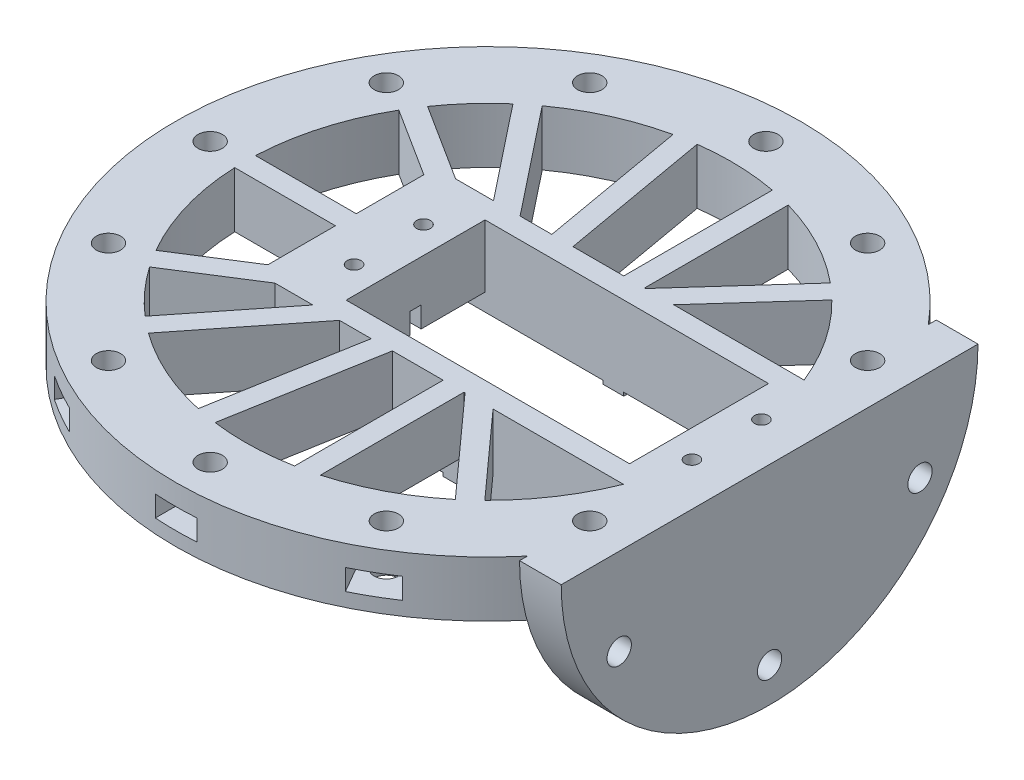
SolidWorks part; units mm, degrees
ref_plane "Front Plane" through (0, 0, 0) normal (0, 0, 1) x (1, 0, 0)
ref_plane "Top Plane" through (0, 0, 0) normal (0, 1, 0) x (1, 0, 0)
ref_plane "Right Plane" through (0, 0, 0) normal (1, 0, 0) x (0, 0, -1)
sketch "Sketch1" plane through (0, 0, 0) normal (0, 1, 0) x (1, 0, 0)
  line L0 (-43.0464, 0) -> (41.9462, 0) construction
  line L1 (0, 43.1152) -> (0, -41.8775) construction
  circle A1 centre (0, 0) radius 45
  dimension "D2" = 90
extrude "Boss-Extrude1" add sketch "Sketch1" along normal blind 12
sketch "Sketch2" plane through (0, 0, 0) normal (0, -1, 0) x (1, 0, 0)
  circle A0 centre (0, 0) radius 35
  dimension "D1" = 70
extrude "Cut-Extrude1" cut sketch "Sketch2" against normal blind 0.5
sketch "Sketch3" plane through (0, 0.5, 0) normal (0, -1, 0) x (1, 0, 0)
  line L0 (35, 0) -> (-35, 0) construction
  line L1 (0, -35) -> (0, 35) construction
  line L3 (37.5324, -10) -> (-17.4676, -10)
  line L4 (37.5324, -10) -> (37.5324, 10)
  line L5 (37.5324, 10) -> (-17.4676, 10)
  line L6 (-17.4676, -10) -> (-17.4676, 10)
  circle A0 centre (0, 0) radius 35 construction
  circle A1 centre (0, 0) radius 35 construction
  dimension "D1" = 20
  dimension "D2" = 55
  dimension "D3" = 10
  dimension "D4" = 37.5324
extrude "Cut-Extrude2" cut sketch "Sketch3" against normal blind 2.5 and the other way up to next
sketch "Sketch4" plane through (0, 3, 0) normal (0, -1, 0) x (1, 0, 0)
  line L0 (37.5324, 0) -> (-17.4676, 0) construction
  line L1 (37.5324, 10) -> (37.5324, -10) construction
  line L2 (-17.4676, 10) -> (-17.4676, -10) construction
  line L3 (0, -10) -> (0, 10) construction
  line L4 (-17.4676, -10) -> (33.541, -10) construction
  line L5 (33.541, 10) -> (-17.4676, 10) construction
  line L7 (30.3722, -10) -> (-10.4278, -10)
  line L8 (30.3722, -10) -> (30.3722, 10)
  line L9 (30.3722, 10) -> (-10.4278, 10)
  line L10 (-10.4278, -10) -> (-10.4278, 10)
  dimension "D1" = 20
  dimension "D2" = 40.8
  dimension "D3" = 30.3722
  dimension "D4" = 10
extrude "Cut-Extrude3" cut sketch "Sketch4" against normal blind 9
sketch "Sketch8" plane through (0, 0.5, 0) normal (0, -1, 0) x (1, 0, 0)
  line L0 (-17.4676, 0) -> (-35, 0) construction
  line L1 (-17.4676, 10) -> (-17.4676, -10) construction
  line L2 (8.0367, 10) -> (8.0367, 34.0648) construction
  line L3 (33.541, 10) -> (-17.4676, 10) construction
  line L4 (8.0367, -10) -> (8.0367, -29.3194) construction
  line L5 (-17.4676, -10) -> (33.541, -10) construction
  line L6 (6.5367, 10) -> (6.5367, 34.3842)
  line L7 (9.5367, 10) -> (9.5367, 33.6757)
  line L8 (9.5367, 10) -> (6.5367, 10)
  line L9 (9.5367, -10) -> (6.5367, -10)
  line L10 (6.5367, -10) -> (6.5367, -34.3842)
  line L11 (9.5367, -10) -> (9.5367, -33.6757)
  line L12 (-17.4676, 1.5) -> (-34.9678, 1.5)
  line L13 (-17.4676, -1.5) -> (-34.9678, -1.5)
  line L14 (-17.4676, 1.5) -> (-17.4676, -1.5)
  arc A0 (33.541, 10) -> (33.541, -10) centre (0, 0) ccw construction
  arc A1 (9.5367, 33.6757) -> (6.5367, 34.3842) centre (7.9531, 33.6757) ccw
  arc A2 (9.5367, -33.6757) -> (6.5367, -34.3842) centre (7.9531, -33.6757) cw
  arc A3 (-34.9678, 1.5) -> (-34.9678, -1.5) centre (-34.9678, 0) ccw
  dimension "D3" = 1.5
  dimension "D1" = 1.5
  dimension "D2" = 1.5
  dimension "D4" = 1.5
extrude "Boss-Extrude2" add sketch "Sketch8" along normal through all
sketch "Sketch16" plane through (0, 3, 0) normal (0, -1, 0) x (1, 0, 0)
  line L0 (-17.4676, 0) -> (37.5324, 0) construction
  line L1 (-17.4676, 10) -> (-17.4676, -10) construction
  line L2 (37.5324, -10) -> (37.5324, 10) construction
  line L3 (30.3722, -0.8) -> (37.5324, -0.8)
  line L4 (-10.4278, -0.8) -> (-17.4676, -0.8)
  line L5 (-10.4278, 10) -> (-10.4278, -10) construction
  line L6 (-10.4278, 0.8) -> (-17.4676, 0.8)
  line L7 (-17.4676, 0.8) -> (-17.4676, -0.8)
  line L8 (-10.4278, 0.8) -> (-10.4278, -0.8)
  line L9 (30.3722, -10) -> (30.3722, 10) construction
  line L10 (30.3722, 0.8) -> (37.5324, 0.8)
  line L11 (37.5324, 0.8) -> (37.5324, -0.8)
  line L12 (30.3722, 0.8) -> (30.3722, -0.8)
  dimension "D1" = 0.8
extrude "Cut-Extrude10" cut sketch "Sketch16" against normal blind 3
sketch "Sketch27" plane through (0, 0, 0) normal (0, -1, 0) x (1, 0, 0)
  line L0 (0, 0) -> (0, -53.17) construction
  line L1 (0, 0) -> (47.7582, -27.5732) construction
  line L3 (31.641, -18.2679) -> (31.641, -21.7321) construction
  line L4 (31.641, -21.7321) -> (34.641, -23.4641) construction
  line L5 (34.641, -23.4641) -> (37.641, -21.7321) construction
  line L6 (37.641, -21.7321) -> (37.641, -18.2679) construction
  line L7 (37.641, -18.2679) -> (34.641, -16.5359) construction
  line L8 (34.641, -16.5359) -> (31.641, -18.2679) construction
  circle A0 centre (0, 0) radius 40 construction
  circle A1 centre (34.641, -20) radius 1.75
  circle A2 centre (0, 0) radius 35 construction
  circle A3 centre (34.641, -20) radius 3 construction
  circle A4 centre (20, -34.641) radius 1.75
  circle A5 centre (0, -40) radius 1.75
  circle A6 centre (-20, -34.641) radius 1.75
  circle A7 centre (-34.641, -20) radius 1.75
  circle A8 centre (-40, 0) radius 1.75
  circle A9 centre (-34.641, 20) radius 1.75
  circle A10 centre (-20, 34.641) radius 1.75
  circle A11 centre (0, 40) radius 1.75
  circle A12 centre (20, 34.641) radius 1.75
  circle A13 centre (34.641, 20) radius 1.75
  circle A15 centre (40, 0) radius 1.75 [skipped]
  point P28 (0, 0)
  point P41 (0, 0)
  dimension "D1" = 80
  dimension "D3" = 3.5
  dimension "D4" = 70
  dimension "D5" = 6
  dimension "D6" = 12
  dimension "D2" = 60
extrude "Cut-Extrude15" cut sketch "Sketch27" against normal through all
ref_plane "Plane1" through (0, 9, 0) normal (0, 1, 0) x (1, 0, 0)
sketch "Sketch28" plane through (0, 9, 0) normal (0, 1, 0) x (1, 0, 0)
  line L0 (0, 0) -> (-54.493, 0) construction
  line L1 (-31.641, 18.2679) -> (-31.641, 21.7321)
  line L2 (-36.5359, 0) -> (-38.2679, 3)
  line L3 (-38.2679, 3) -> (-44.8999, 3)
  line L4 (-31.641, 21.7321) -> (-37.3844, 25.048)
  line L5 (-40.3844, 19.8519) -> (-34.641, 16.5359)
  line L6 (-44.8999, -3) -> (-38.2679, -3)
  line L7 (-38.2679, -3) -> (-36.5359, 0)
  line L8 (-43.4641, 0) -> (-42.5981, -1.5) [skipped]
  line L9 (-41.7321, 3) -> (-42.5981, 1.5) [skipped]
  line L10 (-34.641, 16.5359) -> (-31.641, 18.2679)
  line L11 (-18.2679, 31.641) -> (-16.5359, 34.641)
  line L12 (-16.5359, 34.641) -> (-19.8519, 40.3844)
  line L13 (-25.048, 37.3844) -> (-21.7321, 31.641)
  line L14 (-21.7321, 31.641) -> (-18.2679, 31.641)
  line L15 (0, 36.5359) -> (3, 38.2679)
  line L16 (3, 38.2679) -> (3, 44.8999)
  line L17 (-3, 44.8999) -> (-3, 38.2679)
  line L18 (-3, 38.2679) -> (0, 36.5359)
  line L19 (18.2679, 31.641) -> (21.7321, 31.641)
  line L20 (21.7321, 31.641) -> (25.048, 37.3844)
  line L21 (19.8519, 40.3844) -> (16.5359, 34.641)
  line L22 (16.5359, 34.641) -> (18.2679, 31.641)
  line L23 (31.641, 18.2679) -> (34.641, 16.5359)
  line L24 (34.641, 16.5359) -> (40.3844, 19.8519)
  line L25 (37.3844, 25.048) -> (31.641, 21.7321)
  line L26 (31.641, 21.7321) -> (31.641, 18.2679)
  line L31 (31.641, -18.2679) -> (31.641, -21.7321)
  line L32 (31.641, -21.7321) -> (37.3844, -25.048)
  line L33 (40.3844, -19.8519) -> (34.641, -16.5359)
  line L34 (34.641, -16.5359) -> (31.641, -18.2679)
  line L35 (18.2679, -31.641) -> (16.5359, -34.641)
  line L36 (16.5359, -34.641) -> (19.8519, -40.3844)
  line L37 (25.048, -37.3844) -> (21.7321, -31.641)
  line L38 (21.7321, -31.641) -> (18.2679, -31.641)
  line L39 (0, -36.5359) -> (-3, -38.2679)
  line L40 (-3, -38.2679) -> (-3, -44.8999)
  line L41 (3, -44.8999) -> (3, -38.2679)
  line L42 (3, -38.2679) -> (0, -36.5359)
  line L43 (-18.2679, -31.641) -> (-21.7321, -31.641)
  line L44 (-21.7321, -31.641) -> (-25.048, -37.3844)
  line L45 (-19.8519, -40.3844) -> (-16.5359, -34.641)
  line L46 (-16.5359, -34.641) -> (-18.2679, -31.641)
  line L47 (-31.641, -18.2679) -> (-34.641, -16.5359)
  line L48 (-34.641, -16.5359) -> (-40.3844, -19.8519)
  line L49 (-37.3844, -25.048) -> (-31.641, -21.7321)
  line L50 (-31.641, -21.7321) -> (-31.641, -18.2679)
  line L51 (36.5359, 0) -> (38.2679, -3) [skipped]
  line L52 (38.2679, -3) -> (44.8999, -3) [skipped]
  line L53 (44.8999, 3) -> (38.2679, 3) [skipped]
  line L54 (38.2679, 3) -> (36.5359, 0) [skipped]
  arc A0 (-44.8999, 3) -> (-44.8999, -3) centre (0, 0) ccw
  circle A1 centre (-40, 0) radius 3 construction
  arc A2 (-37.3844, 25.048) -> (-40.3844, 19.8519) centre (0, 0) ccw
  circle A3 centre (-34.641, 20) radius 3 construction
  arc A4 (-19.8519, 40.3844) -> (-25.048, 37.3844) centre (0, 0) ccw
  circle A5 centre (-20, 34.641) radius 3 construction
  arc A6 (3, 44.8999) -> (-3, 44.8999) centre (0, 0) ccw
  circle A7 centre (0, 40) radius 3 construction
  arc A8 (25.048, 37.3844) -> (19.8519, 40.3844) centre (0, 0) ccw
  circle A9 centre (20, 34.641) radius 3 construction
  arc A10 (40.3844, 19.8519) -> (37.3844, 25.048) centre (0, 0) ccw
  circle A11 centre (34.641, 20) radius 3 construction
  arc A14 (37.3844, -25.048) -> (40.3844, -19.8519) centre (0, 0) ccw
  circle A15 centre (34.641, -20) radius 3 construction
  arc A16 (19.8519, -40.3844) -> (25.048, -37.3844) centre (0, 0) ccw
  circle A17 centre (20, -34.641) radius 3 construction
  arc A18 (-3, -44.8999) -> (3, -44.8999) centre (0, 0) ccw
  circle A19 centre (0, -40) radius 3 construction
  arc A20 (-25.048, -37.3844) -> (-19.8519, -40.3844) centre (0, 0) ccw
  circle A21 centre (-20, -34.641) radius 3 construction
  arc A22 (-40.3844, -19.8519) -> (-37.3844, -25.048) centre (0, 0) ccw
  circle A23 centre (-34.641, -20) radius 3 construction
  arc A24 (44.8999, -3) -> (44.8999, 3) centre (0, 0) ccw [skipped]
  circle A25 centre (40, 0) radius 3 construction
  point P94 (0, 0)
  dimension "D1" = 90
  dimension "D2" = 6
  dimension "D3" = 12
extrude "Cut-Extrude17" cut sketch "Sketch28" against normal blind 3
sketch "Sketch29" plane through (0, 0.5, 0) normal (0, -1, 0) x (1, 0, 0)
  line L0 (32.4962, -13) -> (13.7255, -13)
  line L1 (9.5367, -33.6757) -> (9.5367, -10) construction
  line L2 (9.5367, -13) -> (9.5367, -33.6757)
  line L3 (9.5367, -10) -> (33.541, -10) construction
  line L4 (6.5367, -13) -> (-0.7691, -13)
  line L5 (6.5367, -10) -> (6.5367, -34.3842) construction
  line L6 (-20.4676, -11.223) -> (-20.4676, -1.5)
  line L7 (-34.9678, -1.5) -> (-17.4676, -1.5) construction
  line L8 (-20.4676, -1.5) -> (-34.9678, -1.5)
  line L9 (-17.4676, -0.8) -> (-17.4676, -10) construction
  line L10 (32.4962, 13) -> (13.7255, 13)
  line L11 (9.5367, 10) -> (9.5367, 33.6757) construction
  line L12 (9.5367, 13) -> (9.5367, 33.6757)
  line L13 (-7.5493, 34.1761) -> (-3.8154, 13)
  line L14 (6.5367, 13) -> (-0.7691, 13)
  line L15 (6.5367, 34.3842) -> (6.5367, 10) construction
  line L16 (-20.4676, 11.223) -> (-20.4676, 1.5)
  line L17 (-17.4676, 1.5) -> (-34.9678, 1.5) construction
  line L18 (-20.4676, 1.5) -> (-34.9678, 1.5)
  line L19 (6.5367, 13) -> (6.5367, 34.3842)
  line L20 (6.5367, -34.3842) -> (6.5367, -13)
  line L21 (0, 0) -> (-21.7353, -27.4331) construction
  line L22 (-20.5397, -28.3394) -> (-8.3862, -13)
  line L23 (-22.8911, -26.4764) -> (-12.2137, -13)
  line L24 (0, 0) -> (-20.4676, -13) construction
  line L25 (-17.6698, -13) -> (-28.713, -20.0141)
  line L26 (-20.4676, -11.223) -> (-30.3215, -17.4817)
  line L27 (0, 0) -> (-35, 0) construction
  line L28 (-20.4676, 11.223) -> (-30.3215, 17.4817)
  line L29 (-17.6698, 13) -> (-28.713, 20.0141)
  line L30 (-22.8911, 26.4764) -> (-12.2137, 13)
  line L31 (-20.5397, 28.3394) -> (-8.3862, 13)
  line L32 (-12.2137, 13) -> (-17.6698, 13)
  line L33 (0, 0) -> (-6.0777, -34.4683) construction
  line L34 (-4.5949, -34.6971) -> (-0.7691, -13)
  line L35 (-7.5493, -34.1761) -> (-3.8154, -13)
  line L36 (-3.8154, -13) -> (-17.6698, -13)
  line L37 (-4.5949, 34.6971) -> (-0.7691, 13)
  line L38 (-3.8154, 13) -> (-8.3862, 13)
  line L39 (0, 0) -> (23.4214, -26.0084) construction
  line L40 (9.6883, -13) -> (22.2852, -26.9883)
  line L41 (13.7255, -13) -> (24.5145, -24.9808)
  line L42 (13.7255, 13) -> (24.5145, 24.9808)
  line L43 (9.6883, 13) -> (22.2852, 26.9883)
  line L44 (9.6883, -13) -> (9.5367, -13)
  line L45 (9.6883, 13) -> (9.5367, 13)
  arc A0 (9.5367, -33.6757) -> (22.2852, -26.9883) centre (0, 0) ccw
  arc A1 (6.5367, 34.3842) -> (-4.5949, 34.6971) centre (0, 0) ccw
  arc A2 (32.4962, 13) -> (24.5145, 24.9808) centre (0, 0) ccw
  arc A3 (-34.9678, -1.5) -> (-30.3215, -17.4817) centre (0, 0) ccw
  circle A4 centre (0, 0) radius 35 construction
  arc A5 (-7.5493, 34.1761) -> (-20.5397, 28.3394) centre (0, 0) ccw
  arc A6 (-4.5949, -34.6971) -> (6.5367, -34.3842) centre (0, 0) ccw
  arc A7 (-20.5397, -28.3394) -> (-7.5493, -34.1761) centre (0, 0) ccw
  arc A8 (-28.713, -20.0141) -> (-22.8911, -26.4764) centre (0, 0) ccw
  arc A9 (-30.3215, 17.4817) -> (-34.9678, 1.5) centre (0, 0) ccw
  arc A10 (-22.8911, 26.4764) -> (-28.713, 20.0141) centre (0, 0) ccw
  arc A11 (24.5145, -24.9808) -> (32.4962, -13) centre (0, 0) ccw
  arc A12 (22.2852, 26.9883) -> (9.5367, 33.6757) centre (0, 0) ccw
  point P11 (21.5389, -10)
  point P23 (-17.4676, -5.4)
  line M3 (-17.4676, -1.5) -> (-34.9678, -1.5)
  arc M4 (-34.9678, -1.5) -> (6.5367, -34.3842) centre (0, 0) ccw
  line M5 (6.5367, -34.3842) -> (6.5367, -10)
  dimension "D1" = 1.5
  dimension "D2" = 3
  dimension "D3" = 3
  dimension "D4" = 80
  dimension "D5" = 1.5
  dimension "D6" = 1.5
  dimension "D7" = 1.5
sketch "Sketch32" plane through (0, 3, 0) normal (0, -1, 0) x (1, 0, 0)
  line L0 (-17.4676, 0) -> (37.5324, 0) construction
  line L1 (-17.4676, -1.5) -> (-17.4676, 1.5) construction
  line L2 (37.5324, 10) -> (37.5324, -10) construction
  line L3 (10.0324, 0) -> (10.0324, -10) construction
  line L6 (9.5367, -10) -> (33.541, -10) construction
  circle A0 centre (-14.2876, -5) radius 1
  circle A1 centre (-14.2876, 5) radius 1
  circle A2 centre (34.3524, -5) radius 1
  circle A3 centre (34.3524, 5) radius 1
  dimension "D1" = 24.32
  dimension "D3" = 2
  dimension "D2" = 5
extrude "Cut-Extrude21" cut sketch "Sketch32" against normal through all
extrude "Cut-Extrude22" cut sketch "Sketch29" against normal blind 12 contours L28 A9 L18 L16 | L26 L6 M3 M4 | L23 L36 L25 M4 | L35 L36 L22 M4 | L34 L4 M4 M5 | L2 A0 L40 L44 | L41 A11 L0 | L10 A2 L42 | L43 A12 L12 L45 | L19 A1 L37 L14 | L13 A5 L31 L38 | L30 A10 L29 L32 region at (23.89, 0.5, -17.1237) region at (13.9029, 0.5, -24.813) region at (1.8383, 0.5, -24.6789) region at (-27.5459, 0.5, -7.8919) region at (-10.8152, 0.5, -24.1049) region at (-20.9968, 0.5, -18.9781) region at (23.89, 0.5, 17.1237) region at (13.9029, 0.5, 24.813) region at (-10.8152, 0.5, 24.1049) region at (1.8383, 0.5, 24.6789) region at (-27.5459, 0.5, 7.8919) region at (-20.9968, 0.5, 18.9781)
sketch "Sketch33" plane through (0, 0, 0) normal (0, -1, 0) x (1, 0, 0)
  line L0 (37.5324, 0) -> (37.5324, 38.7806) construction
  line L1 (37.5324, 10) -> (37.5324, -10) construction
  line L3 (37.5324, 38.7806) -> (47.0341, 38.7806)
  line L4 (37.5324, 38.7806) -> (37.5324, -37.2389)
  line L5 (37.5324, -37.2389) -> (47.0341, -37.2389)
  line L6 (47.0341, 38.7806) -> (47.0341, -37.2389)
extrude "Cut-Extrude24" cut sketch "Sketch33" against normal through all
sketch "Sketch34" plane through (37.5324, 0, 0) normal (1, 0, 0) x (0, 0, -1)
  line L0 (-24.8258, 12) -> (24.8258, 12) construction
  line L1 (30, 12) -> (-30, 12)
  arc A0 (-30, 12) -> (30, 12) centre (0, 12) ccw
  dimension "D1" = 30
  dimension "D2" = 60
extrude "Boss-Extrude3" add sketch "Sketch34" along normal blind 3
sketch "Sketch35" plane through (37.5324, 0, 0) normal (-1, 0, 0) x (0, 0, 1)
  line L0 (24.8258, 0) -> (10, 0) construction
  line L1 (13, 0) -> (50, 0)
  line L2 (13, 0) -> (13, 4)
  line L3 (13, 4) -> (50, 4)
  line L4 (50, 0) -> (50, 4)
  line L5 (40.3844, 6) -> (37.3844, 6) construction
  line L6 (0, 6) -> (0, 9) construction
  line L7 (-13, 0) -> (-13, 4)
  line L8 (-13, 4) -> (-50, 4)
  line L9 (-13, 0) -> (-50, 0)
  line L10 (-50, 0) -> (-50, 4)
  dimension "D1" = 2
  dimension "D2" = 13
  dimension "D3" = 50
extrude "Cut-Extrude26" cut sketch "Sketch35" along normal blind 90
sketch "Sketch36" plane through (0, 0, 0) normal (0, 0, 1) x (1, 0, 0)
  line L0 (-17.4676, 0) -> (-17.4676, 0.5)
  line L1 (-17.4676, 0.5) -> (-20.4676, 0.5)
  line L2 (-20.4676, 0.5) -> (-23.2653, 4)
  line L3 (-23.2653, 4) -> (-47.4962, 4)
  line L4 (-47.4962, 4) -> (-47.4962, 0)
  line L5 (-47.4962, 0) -> (-17.4676, 0)
  line L6 (-32.4962, 0) -> (-32.4962, 4) construction
  dimension "D1" = 15
extrude "Cut-Extrude27" cut sketch "Sketch36" against normal through all both and the other way through all
sketch "Sketch37" plane through (40.5324, 0, 0) normal (1, 0, 0) x (0, 0, -1)
  line L0 (0, 12) -> (0, -18) construction
  line L1 (30, 12) -> (-30, 12) construction
  arc A0 (-30, 12) -> (30, 12) centre (0, 12) ccw construction
  circle A1 centre (0, -13) radius 1.75
  circle A2 centre (-21.6506, -0.5) radius 1.75
  circle A6 centre (21.6506, -0.5) radius 1.75
  circle A7 centre (-21.6506, 24.5) radius 1.75 [skipped]
  circle A8 centre (0, 37) radius 1.75 [skipped]
  circle A9 centre (21.6506, 24.5) radius 1.75 [skipped]
  point P21 (0, 12)
  dimension "D2" = 3.5
  dimension "D1" = 25
  dimension "D3" = 6
extrude "Cut-Extrude28" cut sketch "Sketch37" against normal up to next
sketch "Sketch44" plane through (37.5324, 0, 0) normal (-1, 0, 0) x (0, 0, 1)
  line L0 (-24.8258, 12) -> (-24.8258, 4)
  line L1 (-24.8258, 4) -> (-13, 4)
  line L2 (-13, 4) -> (-13, 0)
  line L3 (-13, 0) -> (-10, 0)
  line L4 (-10, 0) -> (-10, -16.2843)
  line L5 (-24.8258, 12) -> (-30, 12)
  line L6 (45, 12) -> (-45, 12) construction
  line L7 (0, 12) -> (0, -24.0756) construction
  line L8 (10, 0) -> (10, -16.2843)
  line L9 (13, 0) -> (10, 0)
  line L10 (13, 4) -> (13, 0)
  line L11 (24.8258, 4) -> (13, 4)
  line L12 (24.8258, 12) -> (30, 12)
  line L13 (24.8258, 12) -> (24.8258, 4)
  arc A0 (-30, 12) -> (30, 12) centre (0, 12) ccw construction
  arc A1 (-30, 12) -> (-10, -16.2843) centre (0, 12) ccw
  arc A2 (30, 12) -> (10, -16.2843) centre (0, 12) cw
  circle M8 centre (21.6506, -0.5) radius 1.75
  circle M9 centre (-21.6506, -0.5) radius 1.75
  line M11 (-13, 4) -> (-24.8258, 4)
  line M12 (-24.8258, 4) -> (-24.8258, 6)
  line M16 (-24.8258, 9) -> (-24.8258, 12)
  line M17 (-24.8258, 12) -> (-30, 12)
  arc M18 (-30, 12) -> (30, 12) centre (0, 12) ccw
  line M19 (30, 12) -> (24.8258, 12)
  line M20 (24.8258, 12) -> (24.8258, 9)
  line M24 (24.8258, 6) -> (24.8258, 4)
  line M25 (24.8258, 4) -> (13, 4)
  line M26 (13, 4) -> (13, 0)
  line M27 (13, 0) -> (10, 0)
  line M35 (-10, 0) -> (-13, 0)
  line M36 (-13, 0) -> (-13, 4)
extrude "Boss-Extrude7" add sketch "Sketch44" along normal blind 3 contours L13 L8 M20 M24 M25 M26 M27 M18 M19 M8 | L4 L0 M35 M36 M11 M12 M16 M17 M18 M9 region at (37.5324, -2.5142, 18.844) region at (37.5324, -2.5142, -18.844)
sketch "Sketch45" plane through (34.5324, 0, 0) normal (-1, 0, 0) x (0, 0, 1)
  line L0 (0, 0) -> (0, -20.9828) construction
  circle A0 centre (-21.6506, -0.5) radius 3.25
  circle A1 centre (21.6506, -0.5) radius 3.25
  dimension "D1" = 6.5
extrude "Cut-Extrude30" cut sketch "Sketch45" against normal blind 3
